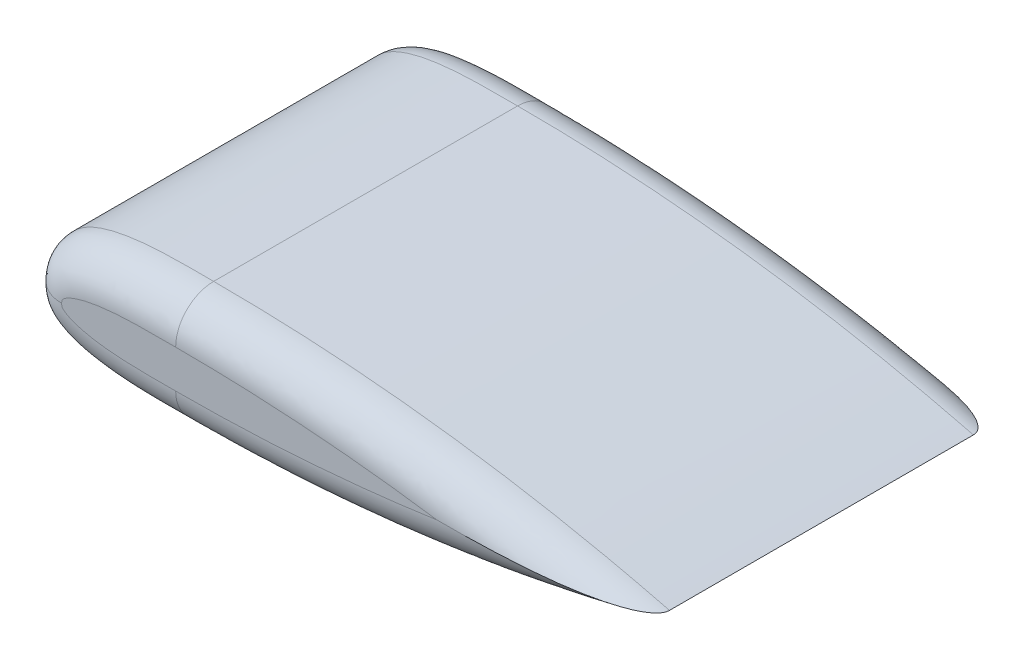
SolidWorks part; units mm, degrees
ref_plane "Front" through (0, 0, 0) normal (0, 0, 1) x (1, 0, 0)
ref_plane "Top" through (0, 0, 0) normal (0, 1, 0) x (1, 0, 0)
ref_plane "Right" through (0, 0, 0) normal (1, 0, 0) x (0, 0, -1)
sketch "Эскиз1" plane through (0, 0, 0) normal (0, 0, 1) x (1, 0, 0)
  line L0 (0, 0) -> (80, 0) construction
  line L1 (0, 0) -> (20, 0) construction
  line L2 (20, 0) -> (20, 7.5) construction
  line L3 (20, 0) -> (20, -7.5) construction
  spline S0 degree 3 poles (0, 0) (0, 7.9753) (12.88, 7.5) (20, 7.5) knots 0 0 0 0 1 1 1 1
  spline S1 degree 2 poles (20, 7.5) (50.2335, 7.5) (80, 0) knots 0 0 0 1 1 1
  spline S2 degree 3 poles (0, 0) (0, -7.9753) (12.88, -7.5) (20, -7.5) knots 0 0 0 0 1 1 1 1
  spline S3 degree 2 poles (20, -7.5) (50.2335, -7.5) (80, 0) knots 0 0 0 1 1 1
  dimension "D1" = 80
  dimension "D2" = 20
  dimension "D3" = 7.5
  dimension "D4" = 7.5
extrude "Бобышка-Вытянуть1" add sketch "Эскиз1" along normal blind 50 contours S1 S3 S2 S0
fillet "Скругление2" radius 5 4 edges
fillet "Скругление3" radius 5 4 edges
